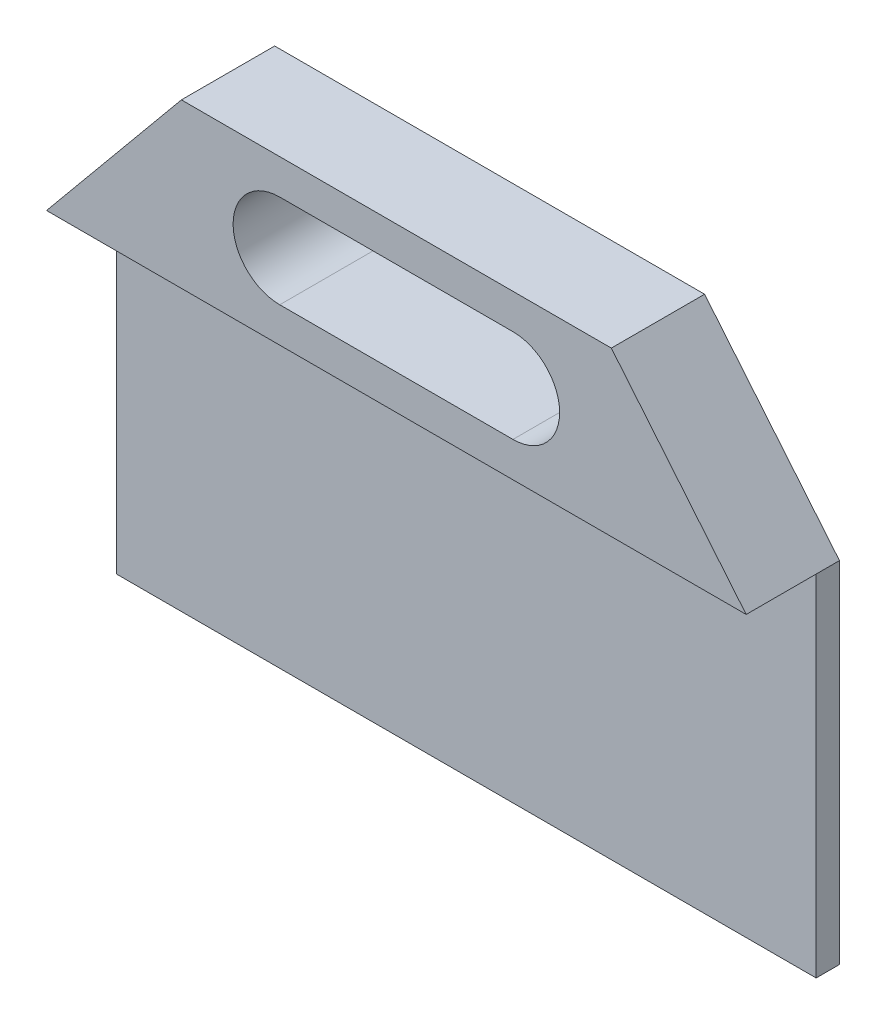
SolidWorks part; units mm, degrees
ref_plane "前视基准面" through (0, 0, 0) normal (0, 0, 1) x (1, 0, 0)
ref_plane "上视基准面" through (0, 0, 0) normal (0, 1, 0) x (1, 0, 0)
ref_plane "右视基准面" through (0, 0, 0) normal (1, 0, 0) x (0, 0, -1)
sketch "草图1" plane through (0, 0, 0) normal (0, 0, 1) x (1, 0, 0)
  line L0 (-15, 7.5) -> (-9.2173, 14.5)
  line L1 (15, -7.5) -> (-15, -7.5)
  line L2 (15, -7.5) -> (15, 7.5)
  line L3 (15, 7.5) -> (-15, 7.5)
  line L4 (-15, -7.5) -> (-15, 7.5)
  line L5 (15, -7.5) -> (-15, 7.5) construction
  line L6 (15, 7.5) -> (-15, -7.5) construction
  line L7 (-9.2173, 14.5) -> (9.2173, 14.5)
  line L8 (0, 25.855) -> (0, -11.3215) construction
  line L9 (15, 7.5) -> (9.2173, 14.5)
  line L10 (-5, 11) -> (5, 11) construction
  line L11 (-5, 13) -> (5, 13)
  line L12 (-5, 9) -> (5, 9)
  arc A0 (-5, 13) -> (-5, 9) centre (-5, 11) ccw
  arc A1 (5, 9) -> (5, 13) centre (5, 11) ccw
  point P0 (0, 0)
  point P11 (0, 14.5)
  point P13 (0, 11)
  point P18 (0, 0)
  dimension "D1" = 4
  dimension "D2" = 10
  dimension "D3" = 7
  dimension "D4" = 3.5
  dimension "D5" = 30
  dimension "D6" = 15
extrude "凸台-拉伸1" add sketch "草图1" along normal blind 1 contours L4 L1 L2 L3 region at (0, 0, 0)
extrude "凸台-拉伸2" add sketch "草图1<3>" along normal blind 4 contours L3 L9 L7 L0 A1 L12 A0 L11 region at (-11.8711, 10.8038, 0)
sketch "草图1<3>" plane through (0, 0, 0) normal (0, 0, 1) x (1, 0, 0) same geometry as "草图1"
